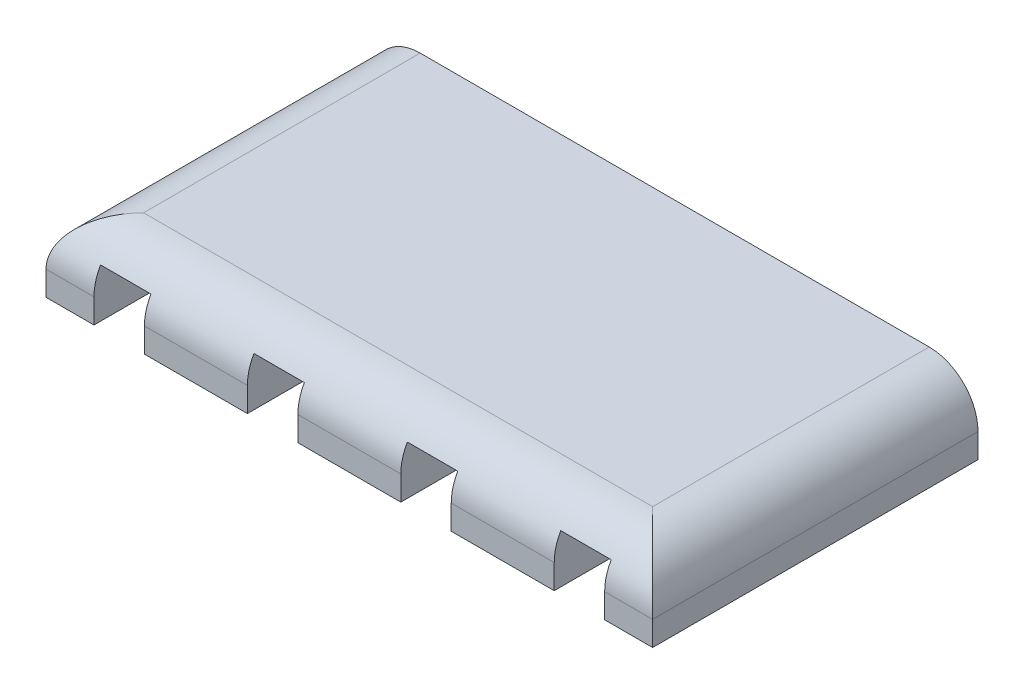
SolidWorks part; units mm, degrees
ref_plane "Front Plane" through (0, 0, 0) normal (0, 0, 1) x (1, 0, 0)
ref_plane "Top Plane" through (0, 0, 0) normal (0, 1, 0) x (1, 0, 0)
ref_plane "Right Plane" through (0, 0, 0) normal (1, 0, 0) x (0, 0, -1)
sketch "Sketch1" plane through (0, 0, 0) normal (0, 0, 1) x (1, 0, 0)
  line L0 (0, 0) -> (0, 4.5)
  line L1 (0, 4.5) -> (37.29, 4.5)
  line L2 (37.29, 4.5) -> (37.29, 0)
  line L3 (37.29, 0) -> (0, 0)
  line L5 (2.95, 0) -> (6.05, 0)
  line L6 (2.95, 0) -> (2.95, 3)
  line L7 (2.95, 3) -> (6.05, 3)
  line L8 (6.05, 0) -> (6.05, 3)
  line L18 (2.075, 0) -> (6.925, 0)
  line L26 (2.075, 0) -> (2.075, 3)
  line L27 (2.075, 3) -> (6.925, 3)
  line L28 (6.925, 0) -> (6.925, 3)
  line L48 (12.38, 0) -> (15.48, 0)
  line L49 (12.38, 0) -> (12.38, 3)
  line L50 (2, 0) -> (7, 0)
  line L51 (2, 0) -> (2, 3.5)
  line L52 (2, 3.5) -> (7, 3.5)
  line L53 (7, 0) -> (7, 3.5)
  line L54 (12.38, 3) -> (15.48, 3)
  line L55 (15.48, 0) -> (15.48, 3)
  line L56 (11.505, 0) -> (16.355, 0)
  line L57 (11.505, 0) -> (11.505, 3)
  line L58 (11.505, 3) -> (16.355, 3)
  line L59 (16.355, 0) -> (16.355, 3)
  line L60 (11.43, 0) -> (16.43, 0)
  line L61 (11.43, 0) -> (11.43, 3.5)
  line L62 (11.43, 3.5) -> (16.43, 3.5)
  line L63 (16.43, 0) -> (16.43, 3.5)
  line L64 (21.81, 0) -> (24.91, 0)
  line L65 (21.81, 0) -> (21.81, 3)
  line L66 (21.81, 3) -> (24.91, 3)
  line L67 (24.91, 0) -> (24.91, 3)
  line L68 (20.935, 0) -> (25.785, 0)
  line L69 (20.935, 0) -> (20.935, 3)
  line L70 (20.935, 3) -> (25.785, 3)
  line L71 (25.785, 0) -> (25.785, 3)
  line L72 (20.86, 0) -> (25.86, 0)
  line L73 (20.86, 0) -> (20.86, 3.5)
  line L74 (20.86, 3.5) -> (25.86, 3.5)
  line L75 (25.86, 0) -> (25.86, 3.5)
  line L76 (31.24, 0) -> (34.34, 0)
  line L77 (31.24, 0) -> (31.24, 3)
  line L78 (31.24, 3) -> (34.34, 3)
  line L79 (34.34, 0) -> (34.34, 3)
  line L80 (30.365, 0) -> (35.215, 0)
  line L81 (30.365, 0) -> (30.365, 3)
  line L82 (30.365, 3) -> (35.215, 3)
  line L83 (35.215, 0) -> (35.215, 3)
  line L84 (30.29, 0) -> (35.29, 0)
  line L85 (30.29, 0) -> (30.29, 3.5)
  line L86 (30.29, 3.5) -> (35.29, 3.5)
  line L87 (35.29, 0) -> (35.29, 3.5)
  line L88 (16.355, 3) -> (20.935, 3) construction
  point P9 (4.5, 3)
  point P10 (18.645, 3)
  point P12 (18.645, 4.5)
  point P17 (4.5, 3)
  point P45 (4.5, 3.5)
  point P58 (13.93, 3.5)
  dimension "D2" = 3.1
  dimension "D3" = 3
  dimension "D4" = 3
  dimension "D5" = 1.5
  dimension "D1" = 4.85
  dimension "D6" = 2
  dimension "D8" = 3.5
  dimension "D9" = 5
  dimension "D10" = 9.43
  dimension "D7" = 4
extrude "Boss-Extrude1" add sketch "Sketch1" along normal blind 20 contours L1 L2 L3 L0
extrude "Cut-Extrude1" cut sketch "Sketch1<3>" along normal through all both and the other way through all contours L77 L78 L79 L76 | L67 L66 L65 L64 | L55 L54 L49 L48 | L8 L7 L6 L5
sketch "Sketch1<3>" plane through (0, 0, 0) normal (0, 0, 1) x (1, 0, 0) same geometry as "Sketch1"
extrude "Cut-Extrude2" cut sketch "Sketch1<4>" along normal blind 5.5 from offset 9 contours L81 L82 L83 L80 | L71 L70 L69 L68 | L59 L58 L57 L56 | L28 L27 L26 L18
sketch "Sketch1<4>" plane through (0, 0, 0) normal (0, 0, 1) x (1, 0, 0) same geometry as "Sketch1"
extrude "Cut-Extrude3" cut sketch "Sketch1<5>" along normal blind 2.5 contours L85 L86 L87 L84 | L75 L74 L73 L72 | L63 L62 L61 L60 | L53 L52 L51 L50
sketch "Sketch1<5>" plane through (0, 0, 0) normal (0, 0, 1) x (1, 0, 0) same geometry as "Sketch1"
fillet "Fillet1" radius 3 3 edges at (18.645, 4.5, 20) (37.29, 4.5, 10) (0, 4.5, 10)
